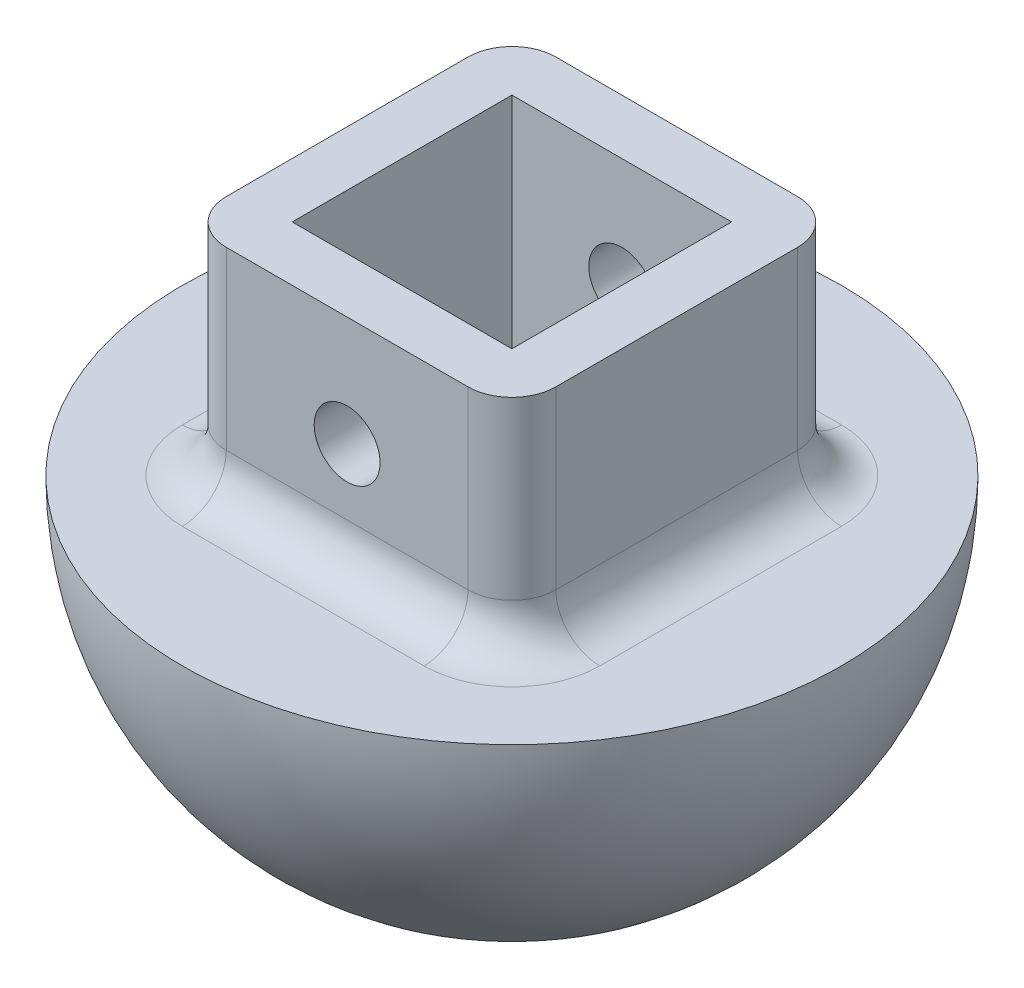
SolidWorks part; units mm, degrees
ref_plane "Front Plane" through (0, 0, 0) normal (0, 0, 1) x (1, 0, 0)
ref_plane "Top Plane" through (0, 0, 0) normal (0, 1, 0) x (1, 0, 0)
ref_plane "Right Plane" through (0, 0, 0) normal (1, 0, 0) x (0, 0, -1)
sketch "Sketch4" plane through (0, 0, 0) normal (0, 1, 0) x (1, 0, 0)
  line L0 (-15, 0) -> (15, 0)
  arc A0 (-15, 0) -> (15, 0) centre (0, 0) ccw
  dimension "D1" = 15
  dimension "D2" = 15
revolve "Revolve2" add sketch "Sketch4" angle 180 about L0 region at (0, 0, 6.3662)
sketch "Sketch1" plane through (0, 0, 0) normal (0, 1, 0) x (1, 0, 0)
  line L1 (-5, 5) -> (5, 5)
  line L2 (-5, 5) -> (-5, -5)
  line L3 (-5, -5) -> (5, -5)
  line L4 (5, 5) -> (5, -5)
  line L5 (-5, 5) -> (5, -5) construction
  line L6 (-5, -5) -> (5, 5) construction
  line L7 (-7.5, 7.5) -> (7.5, 7.5)
  line L8 (-7.5, 7.5) -> (-7.5, -7.5)
  line L9 (-7.5, -7.5) -> (7.5, -7.5)
  line L10 (7.5, 7.5) -> (7.5, -7.5)
  line L11 (-7.5, 7.5) -> (7.5, -7.5) construction
  line L12 (-7.5, -7.5) -> (7.5, 7.5) construction
  point P0 (0, 0)
  point P6 (0, 0)
  dimension "D1" = 10
  dimension "D2" = 15
extrude "Boss-Extrude1" add sketch "Sketch1" along normal blind 10
sketch "Sketch2" plane through (0, 0, 5) normal (0, 0, -1) x (-1, 0, 0)
  line L0 (0, 0) -> (0, 10) construction
  line L1 (-7.5, 10) -> (7.5, 10) construction
  circle A0 centre (0, 5) radius 1.5
  dimension "D1" = 3
extrude "Cut-Extrude1" cut sketch "Sketch2" against normal blind 10 and the other way blind 20
fillet "Fillet1" radius 2 8 edges at (-7.5, 5, 7.5) (-7.5, 5, -7.5) (7.5, 5, -7.5) (7.5, 5, 7.5) (0, 0, -7.5) (7.5, 0, 0) (-7.5, 0, 0) (0, 0, 7.5)
